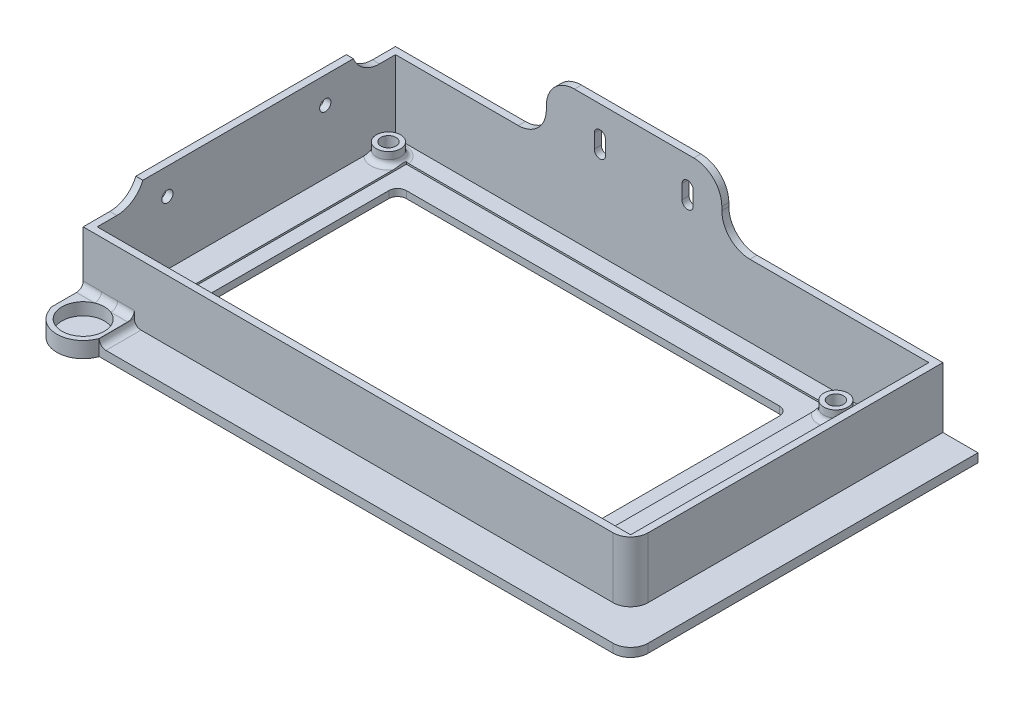
SolidWorks part; units mm, degrees
ref_plane "Alzado" through (0, 0, 0) normal (0, 0, 1) x (1, 0, 0)
ref_plane "Planta" through (0, 0, 0) normal (0, 1, 0) x (1, 0, 0)
ref_plane "Vista lateral" through (0, 0, 0) normal (1, 0, 0) x (0, 0, -1)
sketch "Croquis1" plane through (0, 0, 0) normal (0, 1, 0) x (1, 0, 0)
  line L1 (0, 0) -> (152, 0)
  line L2 (0, 0) -> (0, 85)
  line L3 (0, 85) -> (152, 85)
  line L4 (152, 0) -> (152, 85)
  dimension "D1" = 152
  dimension "D2" = 85
extrude "Saliente-Extruir1" add sketch "Croquis1" along normal blind 1.5
sketch "Croquis2" plane through (0, 1.5, 0) normal (0, 1, 0) x (1, 0, 0)
  line L0 (154, 87) -> (-2, 87)
  line L1 (-2, 87) -> (-2, -2)
  line L2 (-2, -2) -> (154, -2)
  line L3 (154, -2) -> (154, 87)
  line L4 (0, 85) -> (0, 0)
  line L5 (0, 0) -> (152, 0)
  line L6 (152, 0) -> (152, 85)
  line L7 (152, 85) -> (0, 85)
  line L8 (0, 85) -> (0, 0)
  line L9 (0, 0) -> (152, 0)
  line L10 (152, 0) -> (152, 85)
  line L11 (152, 85) -> (0, 85)
  dimension "D1" = 0
  dimension "D2" = 2
extrude "Saliente-Extruir3" add sketch "Croquis2" against normal up to surface (1.5 mm away) and the other way blind 5 up to face at (76, 0, -42.5)
sketch "Croquis3" plane through (0, 1.5, 0) normal (0, 1, 0) x (1, 0, 0)
  line L0 (0, 85) -> (0, 0) construction
  line L1 (152, 85) -> (0, 85) construction
  line L2 (76, 85) -> (76, 0) construction
  line L3 (0, 0) -> (152, 0) construction
  line L4 (0, 42.5) -> (152, 42.5) construction
  line L5 (0, 85) -> (0, 0) construction
  line L6 (152, 0) -> (152, 85) construction
  line L7 (0, 0) -> (152, 0) construction
  circle A0 centre (3.5, 79.5) radius 2.75
  circle A3 centre (3.5, 3.5) radius 3.45
  circle A4 centre (131, 79.5) radius 3.45
  circle A5 centre (131, 3.5) radius 3.45
  circle A6 centre (148.4, 3.5) radius 3.45
  circle A7 centre (148.4, 81.5) radius 3.45
  dimension "D1" = 5.5
  dimension "D4" = 6.9
  dimension "D2" = 3.5
  dimension "D3" = 5.5
  dimension "D5" = 127.5
  dimension "D6" = 5.5
  dimension "D7" = 3.5
  dimension "D8" = 3.5
  dimension "D9" = 3.5
  dimension "D10" = 127.5
  dimension "D11" = 3.6
extrude "Saliente-Extruir4" add sketch "Croquis3" along normal blind 3.5
sketch "Croquis4" plane through (0, 0, 0) normal (0, -1, 0) x (1, 0, 0)
  line L0 (-2, -87) -> (-2, 2) construction
  line L1 (7.6, -80.5) -> (127.1, -80.5)
  line L2 (7.6, -80.5) -> (7.6, -2)
  line L3 (7.6, -2) -> (127.1, -2)
  line L4 (127.1, -80.5) -> (127.1, -2)
  line L5 (154, -87) -> (-2, -87) construction
  dimension "D1" = 119.5
  dimension "D2" = 78.5
  dimension "D3" = 9.6
  dimension "D4" = 6.5
extrude "Cortar-Extruir1" cut sketch "Croquis4" against normal up to surface (1.5 mm away) up to face at (148.4, 1.5, -84.95)
sketch "Croquis5" plane through (0, 5, 0) normal (0, 1, 0) x (1, 0, 0)
  circle A0 centre (131, 3.5) radius 2.15
  circle A1 centre (3.5, 3.5) radius 2.15
  circle A2 centre (3.5, 79.5) radius 2.15
  circle A3 centre (131, 79.5) radius 2.15
  circle A4 centre (148.4, 3.5) radius 2.15
  circle A5 centre (148.4, 81.5) radius 2.15
  dimension "D1" = 4.3
extrude "Cortar-Extruir2" cut sketch "Croquis5" against normal blind 3
sketch "Croquis7" plane through (0, 6.5, 0) normal (0, 1, 0) x (1, 0, 0)
  line L0 (-2, -2) -> (154, -2) construction
  line L1 (0, 0) -> (152, 0) construction
  line L2 (0, 85) -> (0, 0) construction
  line L3 (-2, 87) -> (-2, -2) construction
  line L4 (152, 85) -> (0, 85) construction
  line L5 (154, 87) -> (-2, 87) construction
  line L6 (154, -2) -> (154, 87) construction
  line L7 (152, 0) -> (152, 85) construction
  line L8 (-2, -2) -> (86, -2)
  line L9 (0, 0) -> (86, 0)
  line L10 (0, 85) -> (0, 0)
  line L11 (-2, 87) -> (-2, -2)
  line L12 (152, 85) -> (0, 85)
  line L13 (154, 87) -> (-2, 87)
  line L14 (154, -2) -> (154, 87)
  line L15 (152, 0) -> (152, 85)
  line L16 (86, -2) -> (154, -2)
  line L21 (86, 0) -> (152, 0)
extrude "Saliente-Extruir5" add sketch "Croquis7" along normal blind 15.5
sketch "Croquis9" plane through (0, 22, 0) normal (0, 1, 0) x (1, 0, 0)
  line L1 (93, 85) -> (43, 85)
  line L2 (93, 85) -> (93, 87)
  line L3 (93, 87) -> (43, 87)
  line L4 (43, 85) -> (43, 87)
  line L5 (154, 87) -> (-2, 87) construction
  dimension "D1" = 50
  dimension "D2" = 45
  dimension "D3" = 59
extrude "Saliente-Extruir6" add sketch "Croquis9" along normal blind 17
sketch "Croquis10" plane through (0, 22, 0) normal (0, 1, 0) x (1, 0, 0)
  line L0 (0, 85) -> (0, 0) construction
  line L1 (0, 13) -> (-2, 13)
  line L2 (0, 13) -> (0, 73)
  line L3 (0, 73) -> (-2, 73)
  line L4 (-2, 13) -> (-2, 73)
  line L5 (-2, 87) -> (-2, -2) construction
  line L6 (-2, -2) -> (154, -2) construction
  dimension "D1" = 60
  dimension "D2" = 15
extrude "Saliente-Extruir7" add sketch "Croquis10" along normal blind 5
sketch "Croquis11" plane through (0, 0, 0) normal (1, 0, 0) x (0, 0, -1)
  line L0 (0, 22) -> (0, 1.5) construction
  line L1 (13, 27) -> (73, 27) construction
  circle A0 centre (20, 19.5) radius 1.6
  circle A1 centre (65, 19.5) radius 1.6
  dimension "D1" = 3.2
  dimension "D2" = 45
  dimension "D3" = 20
  dimension "D4" = 7.5
extrude "Cortar-Extruir4" cut sketch "Croquis11" against normal up to surface (2 mm away) up to face at (-2, 17.75, -42.75)
sketch "Croquis12" plane through (0, 0, -85) normal (0, 0, 1) x (1, 0, 0)
  line L0 (93, 39) -> (93, 22) construction
  line L2 (43, 39) -> (93, 39) construction
  circle A0 centre (83.25, 29) radius 1.6
  circle A1 centre (58.25, 29) radius 1.6
  dimension "D2" = 3.2
  dimension "D1" = 10
  dimension "D3" = 9.75
  dimension "D4" = 25
extrude "Cortar-Extruir5" cut sketch "Croquis12" against normal up to surface (2 mm away) up to face at (72, 20.75, -87)
fillet "Redondeo2" radius 8 6 edges at (-1, 22, -73) (-1, 22, -13) (93, 39, -86) (43, 39, -86) (43, 22, -86) (93, 22, -86)
sketch "Croquis13" plane through (0, 0, 2) normal (0, 0, 1) x (1, 0, 0)
  line L0 (-2, 22) -> (-2, 0) construction
  line L1 (-2, 4.75) -> (154, 4.75)
  line L2 (-2, 4.75) -> (-2, 2.25)
  line L3 (-2, 2.25) -> (154, 2.25)
  line L4 (154, 4.75) -> (154, 2.25)
  line L5 (154, 22) -> (154, 0) construction
  line L6 (-2, 0) -> (154, 0) construction
  dimension "D1" = 2.5
  dimension "D2" = 2.25
extrude "Saliente-Extruir8" add sketch "Croquis13" along normal blind 10
sketch "Croquis14" plane through (154, 0, 0) normal (1, 0, 0) x (0, 0, -1)
  line L0 (87, 22) -> (87, 0) construction
  line L1 (-12, 4.75) -> (87, 4.75)
  line L2 (-12, 4.75) -> (-12, 2.25)
  line L3 (-12, 2.25) -> (87, 2.25)
  line L4 (87, 4.75) -> (87, 2.25)
  line L5 (-12, 2.25) -> (-2, 2.25) construction
extrude "Saliente-Extruir9" add sketch "Croquis14" along normal blind 10
fillet "Redondeo3" radius 5 3 edges at (154, 1.125, 2) (164, 3.5, 12) (154, 13.375, 2)
sketch "Croquis15" plane through (0, 4.75, 0) normal (0, 1, 0) x (1, 0, 0)
  line L4 (-2, -2) -> (149, -2) construction
  line L5 (-2, -12) -> (-2, -2) construction
  circle A0 centre (5.5, -9.5) radius 7.5
  dimension "D1" = 15
extrude "Saliente-Extruir10" add sketch "Croquis15" against normal up to surface (2.5 mm away) up to face at (117.7589, 2.25, -17.4911)
sketch "Croquis16" plane through (0, 4.75, 0) normal (0, 1, 0) x (1, 0, 0)
  arc A1 (-1.5711, -12) -> (12.5711, -12) centre (5.5, -9.5) ccw construction
  arc A3 (-1.5711, -12) -> (12.5711, -12) centre (5.5, -9.5) ccw construction
  circle A4 centre (5.5, -9.5) radius 6.05
  dimension "D1" = 12.1
extrude "Cortar-Extruir6" cut sketch "Croquis16" against normal blind 1.5
sketch "Croquis17" plane through (0, 0, 0) normal (0, -1, 0) x (1, 0, 0)
  line L0 (127.1, -2) -> (7.6, -2) construction
  line L1 (127.1, -80.5) -> (127.1, -2) construction
  line L2 (7.6, -2) -> (7.6, -80.5) construction
  line L3 (7.6, -80.5) -> (127.1, -80.5) construction
  line L4 (154, -87) -> (154, -3)
  line L5 (149, 2) -> (-2, 2)
  line L6 (-2, 2) -> (-2, -87)
  line L7 (-2, -87) -> (154, -87)
  line L8 (154, -87) -> (154, -3)
  line L9 (149, 2) -> (-2, 2)
  line L10 (-2, 2) -> (-2, -87)
  line L11 (-2, -87) -> (154, -87)
  line L12 (7.6, -80.5) -> (127.1, -80.5)
  line L13 (7.6, -2) -> (7.6, -80.5)
  line L14 (127.1, -80.5) -> (127.1, -2)
  line L15 (127.1, -2) -> (7.6, -2)
  arc A1 (154, -3) -> (149, 2) centre (149, -3) ccw
  arc A2 (154, -3) -> (149, 2) centre (149, -3) ccw
  dimension "D1" = 0
extrude "Saliente-Extruir11" add sketch "Croquis17" along normal blind 1
sketch "Croquis18" plane through (0, -1, 0) normal (0, -1, 0) x (1, 0, 0)
  line L0 (127.1, -80.5) -> (127.1, -2) construction
  line L1 (7.6, -2) -> (127.1, -2)
  line L2 (7.6, -2) -> (7.6, -6.85)
  line L3 (7.6, -6.85) -> (127.1, -6.85)
  line L4 (127.1, -2) -> (127.1, -6.85)
  line L5 (7.6, -80.5) -> (127.1, -80.5)
  line L6 (7.6, -80.5) -> (7.6, -74)
  line L7 (7.6, -74) -> (127.1, -74)
  line L8 (127.1, -80.5) -> (127.1, -74)
  line L10 (127.1, -2) -> (124.9, -2)
  line L11 (127.1, -2) -> (127.1, -80.5)
  line L12 (127.1, -80.5) -> (124.9, -80.5)
  line L13 (124.9, -2) -> (124.9, -80.5)
  line L14 (7.6, -6.85) -> (9.6, -6.85)
  line L15 (7.6, -6.85) -> (7.6, -74)
  line L16 (7.6, -74) -> (9.6, -74)
  line L17 (9.6, -6.85) -> (9.6, -74)
  line M14 (7.6, -80.5) -> (7.6, -2)
  line M15 (7.6, -2) -> (127.1, -2)
  line M16 (127.1, -2) -> (127.1, -80.5)
  line M17 (127.1, -80.5) -> (7.6, -80.5)
  dimension "D1" = 4.85
  dimension "D2" = 6.5
  dimension "D3" = 2.2
  dimension "D4" = 2
extrude "Saliente-Extruir12" add sketch "Croquis18" against normal blind 2 contours L13 L3 M15 M14 | L17 L3 L7 M14 | L13 L7 L5 M14 | L3 L13 L7 M16 | L1 L13 L3 M16 | L7 L13 M17 M16 region at (66.25, -1, -4.425) region at (126, -1, -4.425) region at (8.6, -1, -40.425) region at (126, -1, -40.425) region at (66.25, -1, -77.25) region at (126, -1, -77.25)
sketch "Croquis19" plane through (0, 1.5, 0) normal (0, 1, 0) x (1, 0, 0)
  circle A0 centre (3.5, 79.5) radius 3.45
  circle A1 centre (3.5, 79.5) radius 2.15 construction
  circle A2 centre (3.5, 79.5) radius 2.15
  dimension "D1" = 6.9
extrude "Saliente-Extruir14" add sketch "Croquis19" along normal up to surface (3.5 mm away) up to face at (3.5, 5, -77.35)
fillet "Redondeo5" radius 1.5 6 edges at (131, 1.5, -82.95) (148.4, 1.5, -84.95) (148.4, 1.5, -6.95) (131, 1.5, -6.95) (3.5, 1.5, -6.95) (3.5, 1.5, -82.95)
sketch "Croquis20" plane through (0, 4.75, 0) normal (0, 1, 0) x (1, 0, 0)
  line L0 (12.5711, -12) -> (12.5711, -2)
  line L1 (149, -2) -> (-2, -2) construction
  line L2 (12.5711, -2) -> (-2, -2)
  line L3 (-2, -2) -> (-2, -12)
  line L4 (-2, -12) -> (-1.5711, -12)
  arc A0 (-1.5711, -12) -> (12.5711, -12) centre (5.5, -9.5) ccw construction
  arc A1 (-1.5711, -12) -> (12.5711, -12) centre (5.5, -9.5) ccw
  circle A2 centre (5.5, -9.5) radius 6.05 construction
  circle A3 centre (5.5, -9.5) radius 6.05
extrude "Saliente-Extruir15" add sketch "Croquis20" along normal blind 2
fillet "Redondeo6" radius 1.9 2 edges at (5.2855, 6.75, 2) (12.5711, 4.75, 7)
fillet "Redondeo7" radius 1.9 1 edges at (-2, 4.5, 12)
sketch "Croquis21" plane through (0, 0, -85) normal (0, 0, 1) x (1, 0, 0)
  line L0 (58.25, 27) -> (58.25, 31) construction
  line L1 (56.65, 27) -> (56.65, 31)
  line L2 (59.85, 27) -> (59.85, 31)
  line L3 (0, 22) -> (0, 1.5) construction
  line L4 (83.25, 27) -> (83.25, 31) construction
  line L5 (81.65, 27) -> (81.65, 31)
  line L6 (84.85, 27) -> (84.85, 31)
  arc A0 (56.65, 27) -> (59.85, 27) centre (58.25, 27) ccw
  arc A1 (59.85, 31) -> (56.65, 31) centre (58.25, 31) ccw
  circle A2 centre (58.25, 29) radius 1.6 construction
  arc A3 (81.65, 27) -> (84.85, 27) centre (83.25, 27) ccw
  arc A4 (84.85, 31) -> (81.65, 31) centre (83.25, 31) ccw
  circle A5 centre (83.25, 29) radius 1.6 construction
  point P2 (58.25, 29)
  point P14 (83.25, 29)
  dimension "D1" = 2
  dimension "D2" = 2
extrude "Cortar-Extruir7" cut sketch "Croquis21" against normal up to surface (2 mm away) up to face at (84.85, 29, -87)
sketch "Croquis22" plane through (0, -1, 0) normal (0, -1, 0) x (1, 0, 0)
  line L0 (9.6, -74) -> (124.9, -74) construction
  line L1 (9.6, -6.85) -> (11.6, -6.85)
  line L2 (9.6, -6.85) -> (9.6, -74)
  line L3 (9.6, -74) -> (11.6, -74)
  line L4 (11.6, -6.85) -> (11.6, -74)
  line L6 (124.9, -6.85) -> (122.9, -6.85)
  line L7 (124.9, -6.85) -> (124.9, -74)
  line L8 (124.9, -74) -> (122.9, -74)
  line L9 (122.9, -6.85) -> (122.9, -74)
  dimension "D1" = 2
  dimension "D2" = 2
extrude "Saliente-Extruir16" add sketch "Croquis22" against normal up to surface (2 mm away) up to face at (67.35, 1, -41.25)
fillet "Redondeo8" radius 2.5 4 edges at (11.6, 0, -74) (122.9, 0, -74) (122.9, 0, -6.85) (11.6, 0, -6.85)
